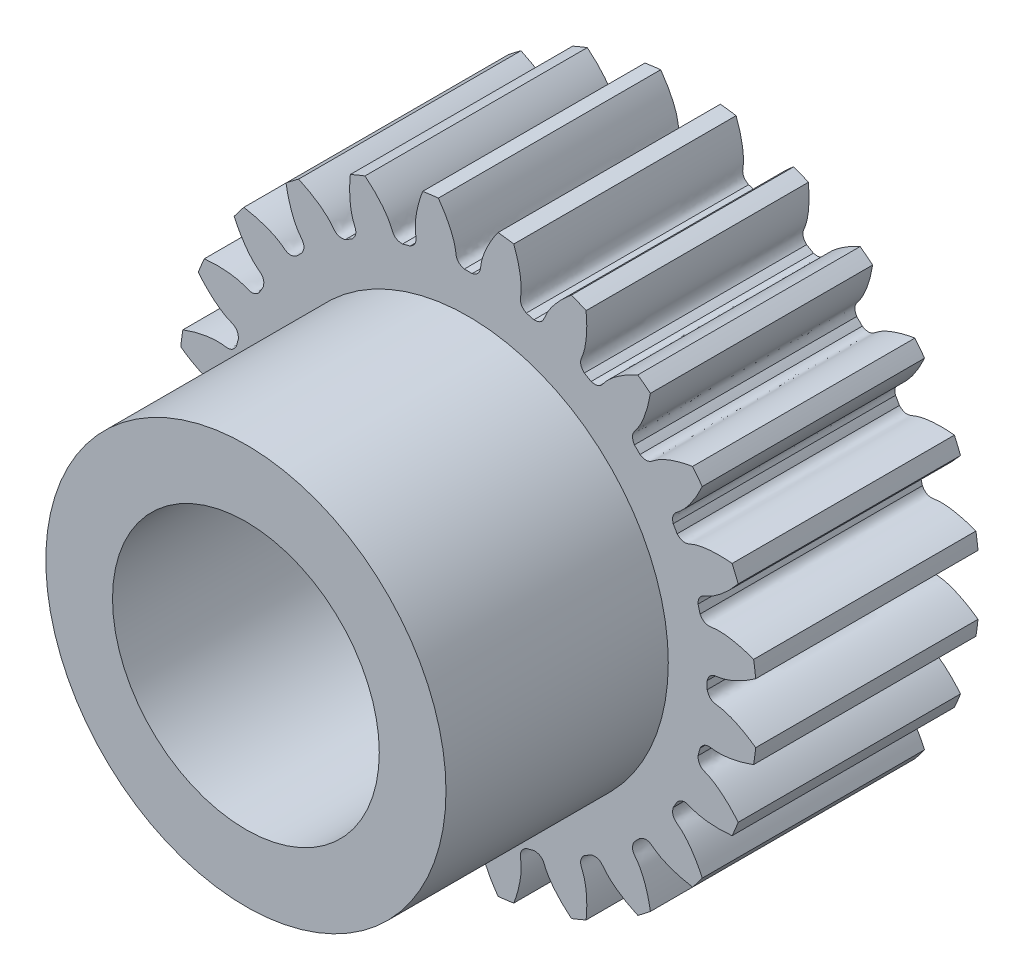
SolidWorks part; units mm, degrees
ref_plane "前视基准面" through (0, 0, 0) normal (0, 0, 1) x (1, 0, 0)
ref_plane "上视基准面" through (0, 0, 0) normal (0, 1, 0) x (1, 0, 0)
ref_plane "右视基准面" through (0, 0, 0) normal (1, 0, 0) x (0, 0, -1)
other "Configuration Table"
sketch "草图1" plane through (0, 0, 0) normal (0, 0, 1) x (1, 0, 0)
  circle A0 centre (0, 0) radius 6.5
extrude "凸台-拉伸1" add sketch "草图1" along normal blind 5
ref_axis "基准轴1" through (0, 0, -0.25) along (0, 0, 1)
sketch "草图2" plane through (0, 0, 0) normal (0, 0, 1) x (1, 0, 0)
  line L0 (0, 0) -> (0, 6.5) construction
  circle A0 centre (0, 0) radius 6.5 construction
  arc A1 (0.0884, 5.3743) -> (-0.0884, 5.3743) centre (0, 0) ccw
  arc A2 (1.5578, 7.3471) -> (-1.5578, 7.3471) centre (0, 0) ccw
  spline S0 degree 3 poles (0.0884, 5.3743) (0.284, 5.4284) (0.2695, 5.5579) (0.2931, 5.6863) (0.2965, 5.7029) (0.3007, 5.7216) (0.3058, 5.7424) (0.312, 5.7653) (0.3191, 5.7902) (0.3275, 5.8171) (0.3371, 5.846) (0.348, 5.8769) (0.3604, 5.9096) (0.3742, 5.9441) (0.3896, 5.9805) (0.4067, 6.0185) (0.4254, 6.0583) (0.446, 6.0997) (0.4684, 6.1427) (0.4928, 6.1872) (0.5192, 6.2332) (0.5476, 6.2806) (0.5782, 6.3293) (0.611, 6.3792) (0.6461, 6.4304) (0.6834, 6.4827) (0.7232, 6.536) (0.7654, 6.5903) (0.8101, 6.6456) (0.8574, 6.7016) (0.9073, 6.7583) (0.9598, 6.8158) (1.015, 6.8738) (1.0729, 6.9322) (1.1336, 6.9911) (1.1972, 7.0503) (1.2635, 7.1097) (1.3328, 7.1693) (1.4302, 7.2497) (1.506, 7.3084) (1.5578, 7.3471) knots 0 0 0 0 0.143961 0.149818 0.156577 0.164236 0.172796 0.182258 0.19262 0.203884 0.216049 0.229115 0.243082 0.25795 0.273719 0.290389 0.30796 0.326433 0.345806 0.366081 0.387257 0.409333 0.432311 0.45619 0.48097 0.506651 0.533234 0.560717 0.589101 0.618387 0.648574 0.679661 0.71165 0.74454 0.778331 0.813023 0.848616 0.885111 0.922506 1 1 1 1
  spline S1 degree 3 poles (-0.0884, 5.3743) (-0.284, 5.4284) (-0.2695, 5.5579) (-0.2931, 5.6863) (-0.2965, 5.7029) (-0.3007, 5.7216) (-0.3058, 5.7424) (-0.312, 5.7653) (-0.3191, 5.7902) (-0.3275, 5.8171) (-0.3371, 5.846) (-0.348, 5.8769) (-0.3604, 5.9096) (-0.3742, 5.9441) (-0.3896, 5.9805) (-0.4067, 6.0185) (-0.4254, 6.0583) (-0.446, 6.0997) (-0.4684, 6.1427) (-0.4928, 6.1872) (-0.5192, 6.2332) (-0.5476, 6.2806) (-0.5782, 6.3293) (-0.611, 6.3792) (-0.6461, 6.4304) (-0.6834, 6.4827) (-0.7232, 6.536) (-0.7654, 6.5903) (-0.8101, 6.6456) (-0.8574, 6.7016) (-0.9073, 6.7583) (-0.9598, 6.8158) (-1.015, 6.8738) (-1.0729, 6.9322) (-1.1336, 6.9911) (-1.1972, 7.0503) (-1.2635, 7.1097) (-1.3328, 7.1693) (-1.4302, 7.2497) (-1.506, 7.3084) (-1.5578, 7.3471) knots 0 0 0 0 0.143961 0.149818 0.156577 0.164236 0.172796 0.182258 0.19262 0.203884 0.216049 0.229115 0.243082 0.25795 0.273719 0.290389 0.30796 0.326433 0.345806 0.366081 0.387257 0.409333 0.432311 0.45619 0.48097 0.506651 0.533234 0.560717 0.589101 0.618387 0.648574 0.679661 0.71165 0.74454 0.778331 0.813023 0.848616 0.885111 0.922506 1 1 1 1
extrude "切除-拉伸1" cut sketch "草图2" along normal through all
pattern_circular "阵列(圆周)1" count 24 every 15 about axis through (0, 0, -0.25) along (0, 0, 1) of "切除-拉伸1"
sketch "草图3" plane through (0, 0, 0) normal (0, 0, 1) x (1, 0, 0)
  circle A0 centre (0, 0) radius 6 construction
  dimension "Dn" = 12
sketch "草图4" plane through (0, 0, 5) normal (0, 0, 1) x (1, 0, 0)
  circle A0 centre (0, 0) radius 4.5
  dimension "D1" = 9
extrude "凸台-拉伸2" add sketch "草图4" along normal blind 5
sketch "草图5" plane through (0, 0, 10) normal (0, 0, 1) x (1, 0, 0)
  circle A0 centre (0, 0) radius 3
  dimension "D1" = 6
extrude "切除-拉伸2" cut sketch "草图5" against normal through all
